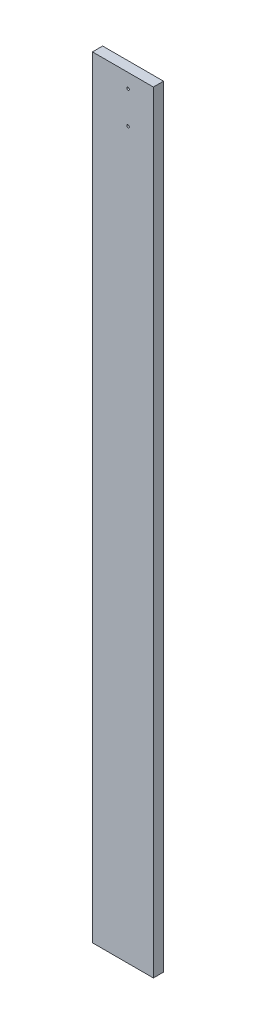
SolidWorks part; units mm, degrees
ref_plane "Front Plane" through (0, 0, 0) normal (0, 0, 1) x (1, 0, 0)
ref_plane "Top Plane" through (0, 0, 0) normal (0, 1, 0) x (1, 0, 0)
ref_plane "Right Plane" through (0, 0, 0) normal (1, 0, 0) x (0, 0, -1)
sketch "Sketch1" plane through (0, 0, 0) normal (0, 0, 1) x (1, 0, 0)
  line L1 (-25.4, -241.3) -> (-25.4, 241.3) construction
  line L2 (-25.4, 241.3) -> (12.7, 241.3)
  line L3 (-25.4, 241.3) -> (-25.4, -241.3)
  line L4 (-25.4, -241.3) -> (12.7, -241.3)
  line L5 (12.7, 241.3) -> (12.7, -241.3)
  point P6 (-25.4, 0)
  dimension "D1" = 482.6
  dimension "D2" = 38.1
  dimension "D3" = 12.7
  dimension "D4" = 241.3
extrude "Boss-Extrude1" add sketch "Sketch1" along normal mid plane 6.35
sketch "Sketch2" plane through (0, 0, 3.175) normal (0, 0, 1) x (1, 0, 0)
  line L0 (12.7, 241.3) -> (-25.4, 241.3) construction
  line L1 (-3.16, 241.3) -> (-3.16, 205.7623) construction
  line L2 (-25.4, 241.3) -> (-25.4, -241.3) construction
  circle A0 centre (-3.16, 232.41) radius 0.7937
  circle A1 centre (-3.16, 212.09) radius 0.7938
  point P10 (0, 0)
  point P11 (-3.16, 214.5157)
  point P12 (0, 0)
  dimension "D3" = 1.5875
  dimension "D1" = 8.89
  dimension "D2" = 20.32
  dimension "D4" = 22.24
extrude "Cut-Extrude1" cut sketch "Sketch2" against normal through all
